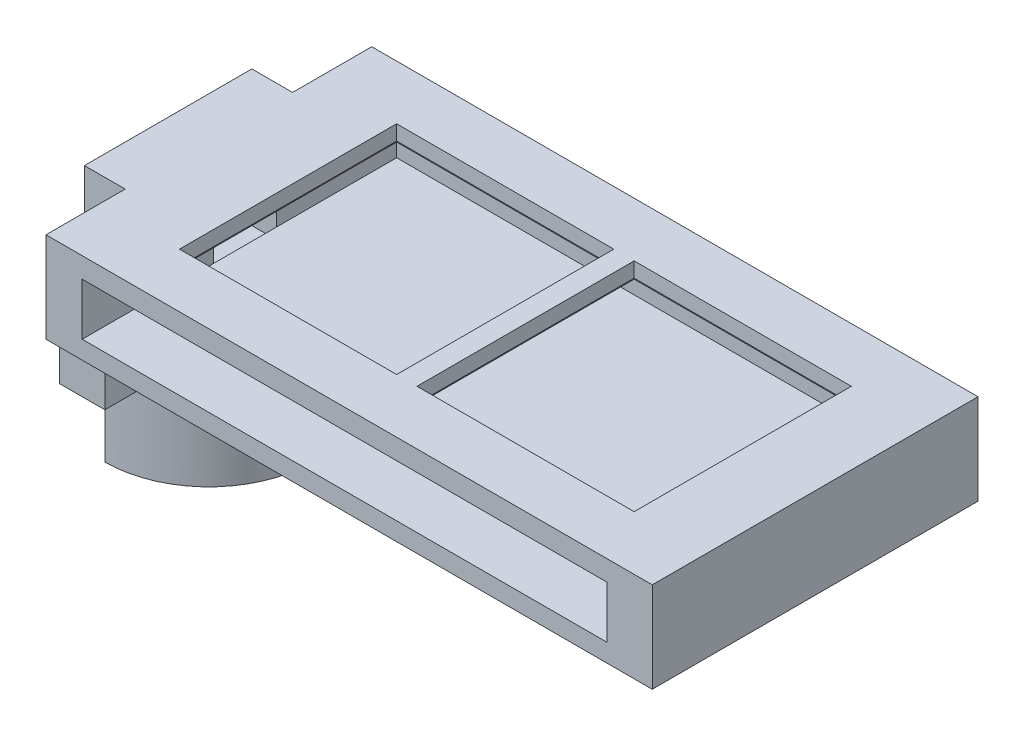
SolidWorks part; units mm, degrees
ref_plane "Front Plane" through (0, 0, 0) normal (0, 0, 1) x (1, 0, 0)
ref_plane "Top Plane" through (0, 0, 0) normal (0, 1, 0) x (1, 0, 0)
ref_plane "Right Plane" through (0, 0, 0) normal (1, 0, 0) x (0, 0, -1)
sketch "Sketch5" plane through (0, 0, 0) normal (0, 1, 0) x (1, 0, 0)
  line L0 (-124, 0) -> (-134, 0)
  line L1 (0, 0) -> (-1.9533, 0)
  line L2 (0, 0) -> (0, 72)
  line L3 (0, 72) -> (-134, 72)
  line L4 (-134, 0) -> (-134, 72)
  line L10 (-124, 0) -> (-1.9533, 0)
  dimension "D1" = 72
  dimension "D2" = 134
extrude "Main Body" add sketch "Sketch5" against normal blind 16 contours L1 L2 L3 L4 region at (-67, 0, -36)
sketch "Sketch8" plane through (0, 0, 0) normal (0, 0, 1) x (1, 0, 0)
  line L0 (-134, -16) -> (-134, 0) construction
  line L1 (0, -16) -> (-134, -16)
  line L2 (0, -16) -> (0, -20)
  line L3 (0, -20) -> (-134, -20)
  line L4 (-134, -16) -> (-134, -20)
  dimension "D1" = 4
extrude "Cover" add sketch "Sketch8" against normal up to surface (72 mm away) up to face at (-67, -8, -72)
sketch "Sketch20" plane through (0, 0, 0) normal (0, 0, 1) x (1, 0, 0)
  line L0 (-134, -20) -> (-134, 0) construction
  line L1 (-10, -4.5) -> (-126, -4.5)
  line L2 (-10, -4.5) -> (-10, -16)
  line L3 (-10, -16) -> (-126, -16)
  line L4 (-126, -4.5) -> (-126, -16)
  line L5 (0, -20) -> (0, 0) construction
  line L7 (-134, -20) -> (0, -20) construction
  dimension "D1" = 8
  dimension "D2" = 10
  dimension "D3" = 11.5
  dimension "D4" = 4
extrude "Crystal Slot" cut sketch "Sketch20" against normal offset from surface (69.5 mm away) 2.5 contours L2 L1 L4 L3 up to face at (-67, -10, -72)
sketch "Sketch9" plane through (-134, 0, 0) normal (-1, 0, 0) x (0, 0, 1)
  line L3 (-29, -4.5) -> (-43, -4.5)
  line L4 (-43, -18.5) -> (-43, -4.5)
  line L5 (-72, -20) -> (-72, 0) construction
  line L6 (-69.5, -4.5) -> (0, -4.5) construction
  line L7 (-29, -4.5) -> (-29, -18.5)
  line L8 (-29, -18.5) -> (-43, -18.5)
  dimension "D1" = 14
  dimension "D2" = 14
  dimension "D3" = 29
  dimension "D4" = 0
extrude "SiPM Window" cut sketch "Sketch9" against normal up to surface (8 mm away) up to face at (-126, -10.25, -34.75)
sketch "Sketch10" plane through (0, -20, 0) normal (0, -1, 0) x (1, 0, 0)
  line L0 (-134, -72) -> (-134, 0) construction
  line L4 (-134, -72) -> (-134, 0) construction
  line L5 (-134, -72) -> (0, -72) construction
  line L6 (-134, -16) -> (-134, -13)
  line L7 (-134, -56) -> (-134, -59)
  arc A0 (-134, -56) -> (-134, -16) centre (-134, -36) ccw
  arc A1 (-134, -59) -> (-134, -13) centre (-134, -36) ccw
  line M4 (-134, 0) -> (-134, -72)
  line M8 (-134, 0) -> (-134, -72)
  dimension "D2" = 20
  dimension "D1" = 36
  dimension "D3" = 3
  dimension "D4" = 3
extrude "Tube Adapter" add sketch "Sketch10" along normal blind 30 contours A1 A0 M4 M8 region at (-133.4857, -20, -14.5)
sketch "Sketch11" plane through (0, -20, 0) normal (0, -1, 0) x (1, 0, 0)
  line L0 (-134, -59) -> (-134, -69)
  line L5 (-134, -72) -> (-134, -59) construction
  line L6 (-134, -69) -> (-124, -69)
  line L7 (-124, -69) -> (-124, -56.7123)
  arc A0 (-134, -59) -> (-124, -56.7123) centre (-134, -36) ccw
  dimension "D1" = 10
  dimension "D2" = 10
extrude "Right Screw Terminal" add sketch "Sketch11" along normal blind 10
sketch "Sketch12" plane through (-134, 0, 0) normal (-1, 0, 0) x (0, 0, 1)
  line L2 (-69, -30) -> (-69, -20) construction
  line L3 (-59, -30) -> (-69, -30) construction
  circle A0 centre (-64, -25) radius 1.524
  dimension "D3" = 5
  dimension "D1" = 3.048
  dimension "D2" = 5
extrude "Right Screw Hole" cut sketch "Sketch12" against normal up to next
sketch "Sketch13" plane through (0, -20, 0) normal (0, -1, 0) x (-1, 0, 0)
  line L2 (134, 13) -> (134, 3)
  line L3 (134, 3) -> (124, 3)
  line L4 (124, 15.2877) -> (124, 3)
  arc A0 (134, 13) -> (124, 15.2877) centre (134, 36) cw
  dimension "D1" = 10
  dimension "D2" = 10
extrude "Left Screw Terminal" add sketch "Sketch13" along normal blind 10
sketch "Sketch14" plane through (-134, 0, 0) normal (-1, 0, 0) x (0, 0, 1)
  line L0 (-3, -30) -> (-3, -20) construction
  line L1 (-3, -30) -> (-13, -30) construction
  circle A0 centre (-8, -25) radius 1.524
  dimension "D3" = 3.048
  dimension "D1" = 5
  dimension "D2" = 5
extrude "Left Screw Hole" cut sketch "Sketch14" against normal up to next
sketch "Sketch15" plane through (-134, 0, 0) normal (-1, 0, 0) x (0, 0, 1)
  line L0 (-56, -20) -> (-16, -20) construction
  line L1 (-17.5, -20) -> (-54.5, -20)
  line L2 (-17.5, -20) -> (-17.5, 0)
  line L3 (-17.5, 0) -> (-54.5, 0)
  line L4 (-54.5, -20) -> (-54.5, 0)
  line L7 (0, 0) -> (-72, 0) construction
  line L8 (-43, -4.5) -> (-43, -18.5) construction
  dimension "D1" = 37
  dimension "D2" = 11.5
extrude "SiPM Mount" add sketch "Sketch15" along normal blind 9
sketch "Sketch17" plane through (0, -20, 0) normal (0, -1, 0) x (1, 0, 0)
  line L1 (-134, -18) -> (-142.8, -18)
  line L3 (-134, -54) -> (-142.8, -54)
  line L4 (-142.8, -18) -> (-142.8, -54)
  line L8 (-134, -18) -> (-134, -54)
  line L10 (-126, -29) -> (-134, -29) construction
  dimension "D1" = 36
  dimension "D2" = 11
  dimension "D3" = 8.8
extrude "SiPM Slot" cut sketch "Sketch17" against normal offset from surface (17.5 mm away) 2 up to face at (-99, -4.5, -35.375) offset beyond the face yes
ref_plane "Plane1" through (-144, 0, 0) normal (-1, 0, 0) x (0, 0, 1)
sketch "Sketch18" plane through (-144, 0, 0) normal (-1, 0, 0) x (0, 0, 1)
  line L0 (-56, -50) -> (-56, -20) construction
  line L5 (-56, -50) -> (-16, -50) construction
  circle A0 centre (-36, -42.5) radius 1.524
  dimension "D1" = 3.048
  dimension "D2" = 20
  dimension "D3" = 7.5
extrude "Adapter Hole" cut sketch "Sketch18" against normal up to surface (32.9495 mm away) up to face at (-124.4677, -32.5, -36)
sketch "Sketch21" plane through (0, -4.5, 0) normal (0, -1, 0) x (1, 0, 0)
  line L0 (-10, -69.5) -> (-10, 0) construction
  line L1 (-15, -11) -> (-65, -11)
  line L2 (-15, -11) -> (-15, -61)
  line L3 (-15, -61) -> (-65, -61)
  line L4 (-65, -11) -> (-65, -61)
  line L5 (-67.5, -11) -> (-117.5, -11)
  line L6 (-67.5, -11) -> (-67.5, -61)
  line L7 (-67.5, -61) -> (-117.5, -61)
  line L8 (-117.5, -11) -> (-117.5, -61)
  line L9 (-65, -36) -> (-15, -36) construction
  line L10 (0, -36) -> (-143, -36) construction
  line L11 (0, -72) -> (0, 0) construction
  line L12 (-143, -54.5) -> (-143, -17.5) construction
  line L13 (-117.5, -36) -> (-67.5, -36) construction
  dimension "D1" = 5
  dimension "D2" = 50
  dimension "D3" = 50
  dimension "D4" = 50
  dimension "D5" = 2.5
  dimension "D6" = 50
extrude "Filter Slot" cut sketch "Sketch21" against normal blind 1.2
sketch "Sketch24" plane through (0, -3.3, 0) normal (0, -1, 0) x (1, 0, 0)
  line L0 (-117.5, -11) -> (-117.5, -61) construction
  line L1 (-16, -12) -> (-64, -12)
  line L2 (-16, -12) -> (-16, -60)
  line L3 (-16, -60) -> (-64, -60)
  line L4 (-64, -12) -> (-64, -60)
  line L5 (-15, -11) -> (-65, -11) construction
  line L7 (-117.5, -61) -> (-67.5, -61) construction
  line L9 (-15, -61) -> (-15, -11) construction
  line L10 (-65, -61) -> (-15, -61) construction
  line L11 (-65, -11) -> (-65, -61) construction
  line L12 (-67.5, -11) -> (-117.5, -11) construction
  line L13 (-116.5, -12) -> (-68.5, -12)
  line L14 (-116.5, -12) -> (-116.5, -60)
  line L15 (-116.5, -60) -> (-68.5, -60)
  line L16 (-68.5, -12) -> (-68.5, -60)
  line L17 (-67.5, -61) -> (-67.5, -11) construction
  dimension "D1" = 1
  dimension "D2" = 1
  dimension "D3" = 1
  dimension "D4" = 1
  dimension "D5" = 1
  dimension "D6" = 1
  dimension "D7" = 1
  dimension "D8" = 1
extrude "Filter Window" cut sketch "Sketch24" against normal up to surface (3.3 mm away) up to face at (-102.75, 0, -36)
